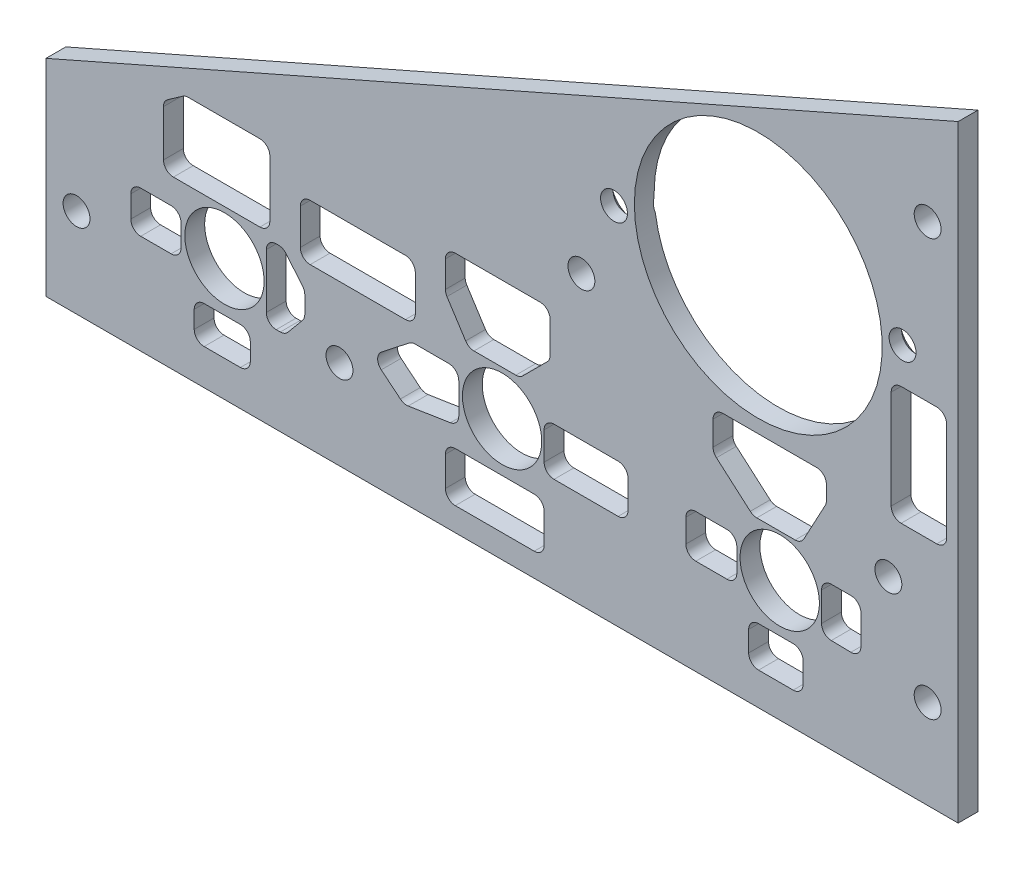
SolidWorks part; units mm, degrees
ref_plane "Front Plane" through (0, 0, 0) normal (0, 0, 1) x (1, 0, 0)
ref_plane "Top Plane" through (0, 0, 0) normal (0, 1, 0) x (1, 0, 0)
ref_plane "Right Plane" through (0, 0, 0) normal (1, 0, 0) x (0, 0, -1)
sketch "Sketch1" plane through (0, 0, 0) normal (0, 0, 1) x (1, 0, 0)
  line L4 (0, 97.282) -> (-146.05, 33.02)
  line L5 (-146.05, 33.02) -> (-146.05, 0)
  line L6 (-146.05, 0) -> (0, 0)
  line L7 (0, 0) -> (0, 97.282)
  line L8 (0, 97.282) -> (-146.05, 33.02)
  line L9 (-146.05, 33.02) -> (-146.05, 0)
  line L10 (-146.05, 0) -> (0, 0)
  line L11 (0, 0) -> (0, 97.282)
  dimension "D1" = 0
extrude "Boss-Extrude1" add sketch "Sketch1" against normal blind 3.175
hole_wizard "#6 Clearance Hole1" positions "Sketch6" profile "Sketch5" hole size "#6" standard "ANSI Inch" end condition through all
sketch "Sketch6" plane through (0, 0, -3.175) normal (0, 0, -1) x (-1, 0, 0)
  point P1 (4.8895, 80.9625)
  point P4 (4.8895, 14.2875)
  point P7 (141.1605, 14.2875)
  point P10 (11.176, 28.575)
  point P12 (60.325, 46.0375)
  point P14 (99.06, 14.2875)
sketch "Sketch5" plane through (-4.8895, 80.9625, -3.175) normal (1, 0, 0) x (0, 1, 0)
  line L0 (0, 0) -> (0, 3.175)
  line L1 (0, 3.175) -> (2.1526, 3.175)
  line L2 (2.1526, 3.175) -> (2.1526, 0)
  line L5 (2.1526, 0) -> (0, 0)
  line L11 (0, -6.35) -> (0, 107.95) construction
  dimension "Thru Hole Dia." = 4.3053
  dimension "Thru Hole Depth" = 3.175
sketch "Sketch7" plane through (0, 0, -3.175) normal (0, 0, -1) x (-1, 0, 0)
  circle A0 centre (32.004, 59.944) radius 19.8438 construction
  circle A1 centre (32.004, 59.944) radius 19.8438
  circle A2 centre (28.575, 19.3759) radius 6.35
  circle A3 centre (73.025, 19.558) radius 6.35
  circle A4 centre (117.475, 19.558) radius 6.35
  ellipse E0 centre (28.575, 21.3285) end of major axis (30.575, 21.3285) minor radius 1.9526 construction
  dimension "D1" = 12.7
extrude "Cut-Extrude1" cut sketch "Sketch7" against normal through all
hole_wizard "CSK for #6 Flat Head Machine Screw (100)1" positions "Sketch8" profile "Sketch9" countersink size "#6" standard "ANSI Inch" end condition up to next
sketch "Sketch8" plane through (0, 0, -3.175) normal (0, 0, -1) x (-1, 0, 0)
  point P0 (8.904, 61.8383)
  point P2 (55.104, 58.0497)
sketch "Sketch9" plane through (-8.904, 61.8383, -3.175) normal (1, 0, 0) x (0, 1, 0)
  line L0 (0, 0) -> (0, 3.175)
  line L1 (0, 3.175) -> (2.1526, 3.175)
  line L2 (2.1526, 3.175) -> (2.1526, 1.1669)
  line L3 (2.1526, 1.1669) -> (3.5433, 0)
  line L5 (3.5433, 0) -> (0, 0)
  line L6 (-2.1526, 1.1669) -> (-3.5433, 0) construction
  line L11 (0, -6.35) -> (0, 107.95) construction
  dimension "Thru Hole Dia." = 4.3053
  dimension "Thru Hole Depth" = 3.175
  dimension "Near C'Sink Dia." = 7.0866
  dimension "Near C'Sink Angle" = 100
sketch "Sketch15" plane through (0, 0, 0) normal (0, 0, -1) x (-1, 0, 0)
  line L0 (3.4308, 55.9821) -> (9.1402, 55.9821)
  line L1 (10.7277, 54.3946) -> (10.7277, 38.5968)
  line L2 (9.1402, 37.0093) -> (3.4308, 37.0093)
  line L3 (1.8433, 38.5968) -> (1.8433, 54.3946)
  line L4 (22.6774, 37.9781) -> (37.6629, 37.9781)
  line L5 (39.2504, 36.3906) -> (39.2504, 32.5074)
  line L6 (38.7044, 31.3093) -> (33.2838, 26.5969)
  line L7 (32.2423, 26.2075) -> (26.1089, 26.2075)
  line L8 (24.7106, 27.0433) -> (21.2791, 33.4267)
  line L9 (21.0899, 34.1784) -> (21.0899, 36.3906)
  line L10 (43.597, 20.6205) -> (43.597, 16.9025)
  line L11 (42.0095, 15.315) -> (37.0319, 15.315)
  line L12 (35.4444, 16.9025) -> (35.4444, 20.6205)
  line L13 (37.0319, 22.208) -> (42.0095, 22.208)
  line L14 (26.4141, 11.6802) -> (31.9586, 11.6802)
  line L15 (33.5461, 10.0927) -> (33.5461, 6.8245)
  line L16 (31.9586, 5.237) -> (26.4141, 5.237)
  line L17 (24.8266, 6.8245) -> (24.8266, 10.0927)
  line L18 (15.5717, 21.3809) -> (15.5717, 16.6831)
  line L19 (17.189, 15.0959) -> (20.3219, 15.1547)
  line L20 (21.8797, 16.7419) -> (21.8797, 21.3809)
  line L21 (20.2922, 22.9684) -> (17.1592, 22.9684)
  line L22 (54.4437, 22.9684) -> (64.7085, 22.9684)
  line L23 (66.296, 21.3809) -> (66.296, 16.9025)
  line L24 (64.7085, 15.315) -> (54.4437, 15.315)
  line L25 (52.8562, 16.9025) -> (52.8562, 21.3809)
  line L26 (67.8835, 11.6802) -> (80.5164, 11.6802)
  line L27 (82.1039, 10.0927) -> (82.1039, 5.3526)
  line L28 (80.5164, 3.7651) -> (67.8835, 3.7651)
  line L29 (66.296, 5.3526) -> (66.296, 10.0927)
  line L30 (79.9618, 21.3647) -> (79.9618, 16.4346)
  line L31 (81.3042, 14.8661) -> (88.0551, 13.8113)
  line L32 (89.3075, 14.1528) -> (92.372, 16.6689)
  line L33 (92.3433, 19.1457) -> (87.9131, 22.6146)
  line L34 (86.9344, 22.9522) -> (81.5493, 22.9522)
  line L35 (65.3361, 37.1822) -> (65.3361, 32.1953)
  line L36 (65.801, 31.0728) -> (69.703, 27.1708)
  line L37 (70.8256, 26.7058) -> (77.5253, 26.7058)
  line L38 (78.8606, 27.4347) -> (81.8516, 32.0861)
  line L39 (82.1039, 32.9447) -> (82.1039, 37.1822)
  line L40 (80.5164, 38.7697) -> (66.9236, 38.7697)
  line L41 (86.9196, 32.8897) -> (86.9196, 27.1599)
  line L42 (88.5071, 25.5724) -> (103.7481, 25.5724)
  line L43 (105.3356, 27.1599) -> (105.3356, 32.8897)
  line L44 (103.7481, 34.4772) -> (88.5071, 34.4772)
  line L45 (110.2115, 37.4103) -> (110.2115, 28.3414)
  line L46 (111.799, 26.7539) -> (125.6537, 26.7539)
  line L47 (127.2412, 28.3414) -> (127.2412, 35.7322)
  line L48 (126.5641, 37.0327) -> (124.167, 38.7108)
  line L49 (123.2566, 38.9978) -> (111.799, 38.9978)
  line L50 (126.0132, 15.9333) -> (130.8857, 15.9333)
  line L51 (132.4732, 17.5208) -> (132.4732, 21.0234)
  line L52 (130.8857, 22.6109) -> (126.0132, 22.6109)
  line L53 (124.4257, 21.0234) -> (124.4257, 17.5208)
  line L54 (114.9274, 11.6802) -> (120.7304, 11.6802)
  line L55 (122.3179, 10.0927) -> (122.3179, 7.3067)
  line L56 (120.7304, 5.7192) -> (114.9274, 5.7192)
  line L57 (113.3399, 7.3067) -> (113.3399, 10.0927)
  line L58 (110.7762, 15.4245) -> (110.7762, 24.1408)
  line L59 (109.1887, 25.7283) -> (108.8288, 25.7283)
  line L60 (107.6065, 25.1537) -> (104.9817, 21.986)
  line L61 (104.6165, 20.9731) -> (104.6165, 18.2321)
  line L62 (104.9816, 17.2192) -> (107.3081, 14.4116)
  line L63 (108.5304, 13.837) -> (109.1887, 13.837)
  line L64 (0, 0) -> (0, 97.282) construction
  line L65 (0, 0) -> (146.05, 0) construction
  arc A1 (104.6165, 18.2321) -> (104.9816, 17.2192) centre (106.204, 18.2321) ccw
  arc A2 (104.9817, 21.986) -> (104.6165, 20.9731) centre (106.204, 20.9731) ccw
  arc A3 (107.3081, 14.4116) -> (108.5304, 13.837) centre (108.5304, 15.4245) ccw
  arc A4 (110.7762, 24.1408) -> (109.1887, 25.7283) centre (109.1887, 24.1408) ccw
  arc A5 (108.8288, 25.7283) -> (107.6065, 25.1537) centre (108.8288, 24.1408) ccw
  arc A6 (110.7762, 15.4245) -> (109.1887, 13.837) centre (109.1887, 15.4245) cw
  arc A7 (126.0132, 22.6109) -> (124.4257, 21.0234) centre (126.0132, 21.0234) ccw
  arc A8 (132.4732, 21.0234) -> (130.8857, 22.6109) centre (130.8857, 21.0234) ccw
  arc A9 (130.8857, 15.9333) -> (132.4732, 17.5208) centre (130.8857, 17.5208) ccw
  arc A10 (126.0132, 15.9333) -> (124.4257, 17.5208) centre (126.0132, 17.5208) cw
  arc A11 (124.167, 38.7108) -> (123.2566, 38.9978) centre (123.2566, 37.4103) ccw
  arc A12 (125.6537, 26.7539) -> (127.2412, 28.3414) centre (125.6537, 28.3414) ccw
  arc A13 (127.2412, 35.7322) -> (126.5641, 37.0327) centre (125.6537, 35.7322) ccw
  arc A14 (110.2115, 28.3414) -> (111.799, 26.7539) centre (111.799, 28.3414) ccw
  arc A15 (105.3356, 32.8897) -> (103.7481, 34.4772) centre (103.7481, 32.8897) ccw
  arc A16 (110.2115, 37.4103) -> (111.799, 38.9978) centre (111.799, 37.4103) cw
  arc A17 (103.7481, 25.5724) -> (105.3356, 27.1599) centre (103.7481, 27.1599) ccw
  arc A18 (86.9196, 27.1599) -> (88.5071, 25.5724) centre (88.5071, 27.1599) ccw
  arc A19 (86.9196, 32.8897) -> (88.5071, 34.4772) centre (88.5071, 32.8897) cw
  arc A20 (82.1039, 37.1822) -> (80.5164, 38.7697) centre (80.5164, 37.1822) ccw
  arc A21 (77.5253, 26.7058) -> (78.8606, 27.4347) centre (77.5253, 28.2933) ccw
  arc A22 (81.8516, 32.0861) -> (82.1039, 32.9447) centre (80.5164, 32.9447) ccw
  arc A23 (69.703, 27.1708) -> (70.8256, 26.7058) centre (70.8256, 28.2933) ccw
  arc A24 (65.3361, 32.1953) -> (65.801, 31.0728) centre (66.9236, 32.1953) ccw
  arc A25 (87.9131, 22.6146) -> (86.9344, 22.9522) centre (86.9344, 21.3647) ccw
  arc A26 (65.3361, 37.1822) -> (66.9236, 38.7697) centre (66.9236, 37.1822) cw
  arc A27 (88.0551, 13.8113) -> (89.3075, 14.1528) centre (88.3002, 15.3797) ccw
  arc A28 (92.372, 16.6689) -> (92.3433, 19.1457) centre (91.3646, 17.8958) ccw
  arc A29 (79.9618, 16.4346) -> (81.3042, 14.8661) centre (81.5493, 16.4346) ccw
  arc A30 (79.9618, 21.3647) -> (81.5493, 22.9522) centre (81.5493, 21.3647) cw
  arc A31 (66.296, 16.9025) -> (64.7085, 15.315) centre (64.7085, 16.9025) cw
  arc A32 (54.4437, 15.315) -> (52.8562, 16.9025) centre (54.4437, 16.9025) cw
  arc A33 (64.7085, 22.9684) -> (66.296, 21.3809) centre (64.7085, 21.3809) cw
  arc A34 (21.8797, 21.3809) -> (20.2922, 22.9684) centre (20.2922, 21.3809) ccw
  arc A35 (54.4437, 22.9684) -> (52.8562, 21.3809) centre (54.4437, 21.3809) ccw
  arc A36 (20.3219, 15.1547) -> (21.8797, 16.7419) centre (20.2922, 16.7419) ccw
  arc A37 (15.5717, 16.6831) -> (17.189, 15.0959) centre (17.1592, 16.6831) ccw
  arc A38 (15.5717, 21.3809) -> (17.1592, 22.9684) centre (17.1592, 21.3809) cw
  arc A39 (33.5461, 6.8245) -> (31.9586, 5.237) centre (31.9586, 6.8245) cw
  arc A40 (26.4141, 5.237) -> (24.8266, 6.8245) centre (26.4141, 6.8245) cw
  arc A41 (31.9586, 11.6802) -> (33.5461, 10.0927) centre (31.9586, 10.0927) cw
  arc A42 (26.4141, 11.6802) -> (24.8266, 10.0927) centre (26.4141, 10.0927) ccw
  arc A43 (35.4444, 20.6205) -> (37.0319, 22.208) centre (37.0319, 20.6205) cw
  arc A44 (37.0319, 15.315) -> (35.4444, 16.9025) centre (37.0319, 16.9025) cw
  arc A45 (43.597, 16.9025) -> (42.0095, 15.315) centre (42.0095, 16.9025) cw
  arc A46 (43.597, 20.6205) -> (42.0095, 22.208) centre (42.0095, 20.6205) ccw
  arc A47 (21.2791, 33.4267) -> (21.0899, 34.1784) centre (22.6774, 34.1784) cw
  arc A48 (26.1089, 26.2075) -> (24.7106, 27.0433) centre (26.1089, 27.795) cw
  arc A49 (39.2504, 32.5074) -> (38.7044, 31.3093) centre (37.6629, 32.5074) cw
  arc A50 (33.2838, 26.5969) -> (32.2423, 26.2075) centre (32.2423, 27.795) cw
  arc A51 (37.6629, 37.9781) -> (39.2504, 36.3906) centre (37.6629, 36.3906) cw
  arc A52 (3.4308, 37.0093) -> (1.8433, 38.5968) centre (3.4308, 38.5968) cw
  arc A53 (22.6774, 37.9781) -> (21.0899, 36.3906) centre (22.6774, 36.3906) ccw
  arc A54 (10.7277, 38.5968) -> (9.1402, 37.0093) centre (9.1402, 38.5968) cw
  arc A55 (9.1402, 55.9821) -> (10.7277, 54.3946) centre (9.1402, 54.3946) cw
  arc A56 (3.4308, 55.9821) -> (1.8433, 54.3946) centre (3.4308, 54.3946) ccw
  arc A57 (114.9274, 5.7192) -> (113.3399, 7.3067) centre (114.9274, 7.3067) cw
  arc A58 (122.3179, 7.3067) -> (120.7304, 5.7192) centre (120.7304, 7.3067) cw
  arc A59 (120.7304, 11.6802) -> (122.3179, 10.0927) centre (120.7304, 10.0927) cw
  arc A60 (114.9274, 11.6802) -> (113.3399, 10.0927) centre (114.9274, 10.0927) ccw
  arc A61 (82.1039, 5.3526) -> (80.5164, 3.7651) centre (80.5164, 5.3526) cw
  arc A62 (67.8835, 3.7651) -> (66.296, 5.3526) centre (67.8835, 5.3526) cw
  arc A63 (80.5164, 11.6802) -> (82.1039, 10.0927) centre (80.5164, 10.0927) cw
  arc A64 (67.8835, 11.6802) -> (66.296, 10.0927) centre (67.8835, 10.0927) ccw
  point P134 (21.8797, 22.9684)
  point P139 (21.8797, 15.1839)
  point P150 (33.5461, 11.6802)
  point P159 (43.597, 15.315)
  point P196 (82.1039, 11.6802)
  dimension "D1" = 1.5875
extrude "Cut-Extrude4" cut sketch "Sketch15" along normal through all
